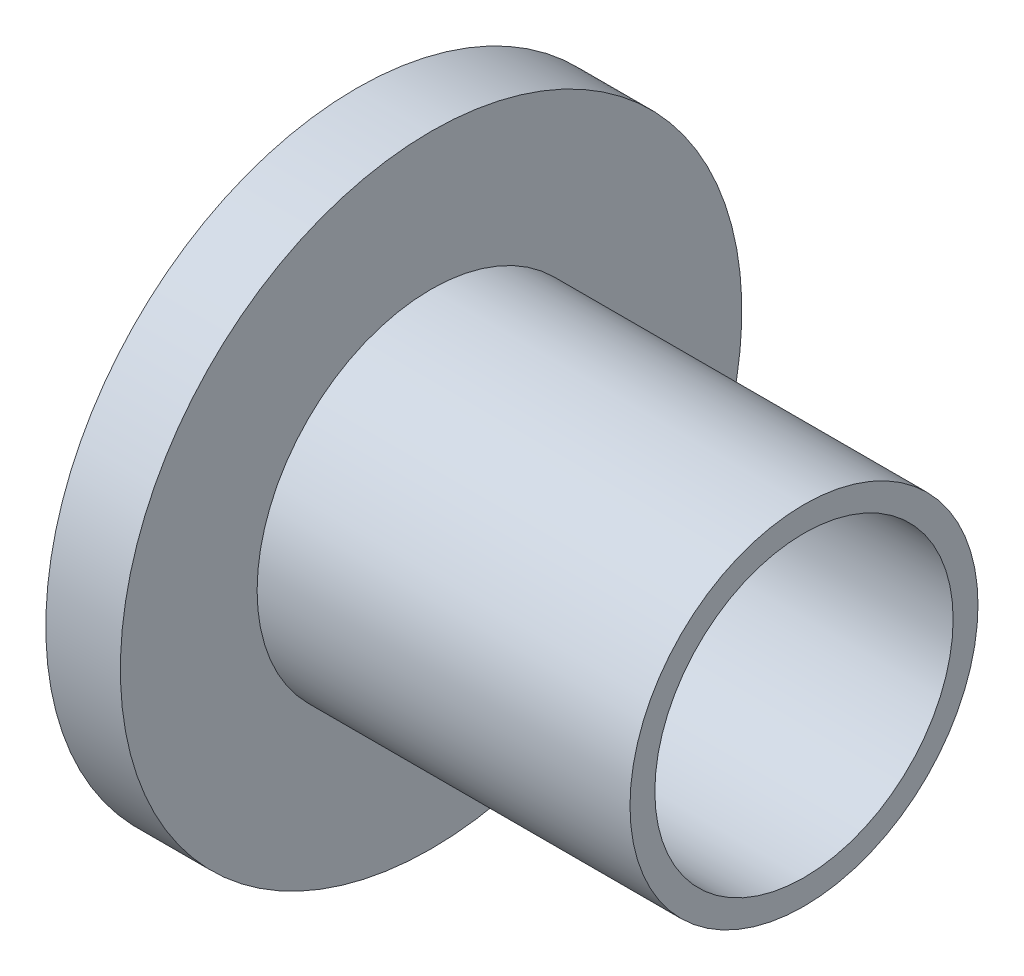
SolidWorks part; units mm, degrees
ref_plane "Front Plane" through (0, 0, 0) normal (0, 0, 1) x (1, 0, 0)
ref_plane "Top Plane" through (0, 0, 0) normal (0, 1, 0) x (1, 0, 0)
ref_plane "Right Plane" through (0, 0, 0) normal (1, 0, 0) x (0, 0, -1)
sketch "Sketch1" plane through (0, 0, 0) normal (0, 0, 1) x (1, 0, 0)
  line L0 (-64.9001, 0) -> (64.9001, 0) construction
  line L1 (-6, 25) -> (-6, 7.5)
  line L2 (-3, 10) -> (0, 10)
  line L3 (0, 10) -> (0, 12)
  line L4 (0, 12) -> (30, 12)
  line L5 (30, 12) -> (30, 14)
  line L6 (30, 14) -> (0, 14)
  line L7 (0, 14) -> (0, 25)
  line L8 (0, 25) -> (-6, 25)
  line L9 (-3, 10) -> (-3, 5.5)
  line L10 (-3, 5.5) -> (-16, 5.5)
  line L11 (-16, 5.5) -> (-16, 7.5)
  line L12 (-16, 7.5) -> (-6, 7.5)
  line L13 (-3, 10) -> (-3, 25) construction
  line L14 (-6, 10) -> (0, 10) construction
  point P3 (0, 0)
  point P6 (-3, 25)
  dimension "D1" = 24
  dimension "D2" = 28
  dimension "D3" = 20
  dimension "D4" = 50
  dimension "D5" = 6
  dimension "D6" = 30
  dimension "D7" = 15
  dimension "D8" = 10
  dimension "D9" = 2
revolve "Revolve1" add sketch "Sketch1" angle 360 about L0
